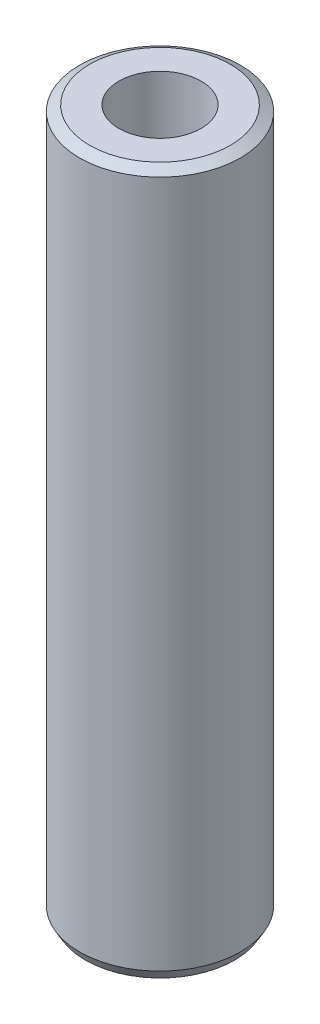
SolidWorks part; units mm, degrees
ref_plane "Front Plane" through (0, 0, 0) normal (0, 0, 1) x (1, 0, 0)
ref_plane "Top Plane" through (0, 0, 0) normal (0, 1, 0) x (1, 0, 0)
ref_plane "Right Plane" through (0, 0, 0) normal (1, 0, 0) x (0, 0, -1)
sketch "Sketch1" plane through (0, 0, 0) normal (0, 1, 0) x (1, 0, 0)
  circle A0 centre (0, 0) radius 37.5
  dimension "SHAFT_OD" = 75
extrude "Boss-Extrude1" add sketch "Sketch1" along normal blind 328.0506
sketch "Sketch2" plane through (0, 0, 0) normal (0, 1, 0) x (1, 0, 0)
  circle A0 centre (0, 0) radius 19.1573
  dimension "BORE_D" = 38.3147
extrude "Cut-Extrude1" cut sketch "Sketch2" along normal through all
chamfer "Chamfer1" distance 2.7258 angle 60 2 edges at (0, 328.0506, 37.5) (0, 0, 37.5) first distance on face at (0, 328.0506, 37.5) first distance on face at (0, 0, 19.1573)
